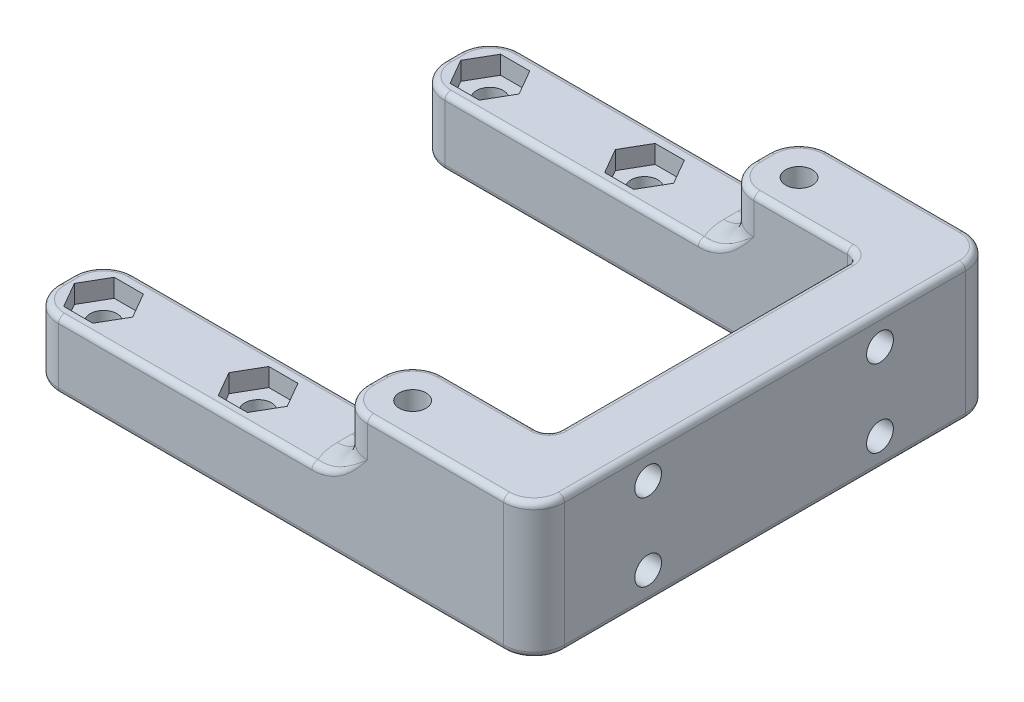
SolidWorks part; units mm, degrees
ref_plane "Front Plane" through (0, 0, 0) normal (0, 0, 1) x (1, 0, 0)
ref_plane "Top Plane" through (0, 0, 0) normal (0, 1, 0) x (1, 0, 0)
ref_plane "Right Plane" through (0, 0, 0) normal (1, 0, 0) x (0, 0, -1)
sketch "Sketch1" plane through (0, 0, 0) normal (0, 1, 0) x (1, 0, 0)
  line L0 (0, 0) -> (73.15, 0)
  line L1 (73.15, 0) -> (73.15, -51.1048)
  line L2 (73.15, -51.1048) -> (0, -51.1048)
  line L3 (0, -51.1048) -> (0, -63.5)
  line L4 (0, -63.5) -> (83.15, -63.5)
  line L5 (83.15, -63.5) -> (83.15, 12.3952)
  line L6 (83.15, 12.3952) -> (0, 12.3952)
  line L7 (0, 12.3952) -> (0, 0)
  circle A0 centre (6.35, 6.0452) radius 2.2
  circle A1 centre (57.15, 6.0452) radius 2.2
  circle A2 centre (6.35, -57.4548) radius 2.2
  circle A3 centre (57.15, -57.4548) radius 2.2
  circle A4 centre (31.75, 6.0452) radius 2.2
  circle A5 centre (31.75, -57.4548) radius 2.2
  point P19 (0, 0)
  point P20 (0, 0)
  point P23 (0, 0)
  dimension "D5" = 4.4
  dimension "D1" = 10
  dimension "D2" = 12.3952
  dimension "D3" = 6.35
  dimension "D4" = 6.35
  dimension "D6" = 50.8
  dimension "D7" = 16
  dimension "D8" = 6.35
  dimension "D9" = 63.5
  dimension "D10" = 25.4
extrude "Boss-Extrude1" add sketch "Sketch1" along normal blind 22.2504
sketch "Sketch2" plane through (0, 0, 63.5) normal (0, 0, 1) x (1, 0, 0)
  line L1 (0, 22.2504) -> (50.8, 22.2504)
  line L2 (0, 22.2504) -> (0, 11.1252)
  line L3 (0, 11.1252) -> (50.8, 11.1252)
  line L4 (50.8, 22.2504) -> (50.8, 11.1252)
  line L5 (0, 0) -> (83.15, 0)
  line L6 (83.15, 0) -> (83.15, 22.2504)
  line L7 (83.15, 22.2504) -> (0, 22.2504)
  line L8 (0, 22.2504) -> (0, 0)
  line L9 (0, 0) -> (83.15, 0)
  line L10 (83.15, 0) -> (83.15, 22.2504)
  line L11 (83.15, 22.2504) -> (0, 22.2504)
  line L12 (0, 22.2504) -> (0, 0)
  point P2 (0, 11.1252)
  point P6 (0, 0)
  point P8 (83.15, 11.1252)
  dimension "D1" = 0
  dimension "D2" = 50.8
extrude "Cut-Extrude1" cut sketch "Sketch2" against normal through all
sketch "Sketch3" plane through (0, 11.1252, 0) normal (0, 1, 0) x (1, 0, 0)
  line L0 (36.542, 6.0452) -> (34.146, 10.1952)
  line L1 (11.142, 6.0452) -> (8.746, 10.1952)
  line L2 (8.746, 10.1952) -> (3.954, 10.1952)
  line L3 (3.954, 10.1952) -> (1.558, 6.0452)
  line L4 (1.558, 6.0452) -> (3.954, 1.8952)
  line L5 (3.954, 1.8952) -> (8.746, 1.8952)
  line L6 (8.746, 1.8952) -> (11.142, 6.0452)
  line L7 (34.146, 10.1952) -> (29.354, 10.1952)
  line L8 (29.354, 10.1952) -> (26.958, 6.0452)
  line L9 (26.958, 6.0452) -> (29.354, 1.8952)
  line L10 (29.354, 1.8952) -> (34.146, 1.8952)
  line L11 (34.146, 1.8952) -> (36.542, 6.0452)
  line L12 (36.542, -57.4548) -> (34.146, -53.3048)
  line L13 (34.146, -53.3048) -> (29.354, -53.3048)
  line L14 (29.354, -53.3048) -> (26.958, -57.4548)
  line L15 (26.958, -57.4548) -> (29.354, -61.6048)
  line L16 (29.354, -61.6048) -> (34.146, -61.6048)
  line L17 (34.146, -61.6048) -> (36.542, -57.4548)
  line L18 (11.142, -57.4548) -> (8.746, -53.3048)
  line L19 (8.746, -53.3048) -> (3.954, -53.3048)
  line L20 (3.954, -53.3048) -> (1.558, -57.4548)
  line L21 (1.558, -57.4548) -> (3.954, -61.6048)
  line L22 (3.954, -61.6048) -> (8.746, -61.6048)
  line L23 (8.746, -61.6048) -> (11.142, -57.4548)
  circle A0 centre (6.35, 6.0452) radius 4.15 construction
  dimension "D3" = 8.3
  dimension "D1" = 2
  dimension "D2" = 2
extrude "Cut-Extrude2" cut sketch "Sketch3" against normal blind 3
fillet "Fillet3" radius 5 4 edges at (0, 5.5626, -12.3952) (0, 5.5626, 0) (0, 5.5626, 51.1048) (0, 5.5626, 63.5)
sketch "Sketch4" plane through (83.15, 0, 0) normal (1, 0, 0) x (0, 0, -1)
  line L0 (-51.1048, 22.2504) -> (-51.1048, 0) construction
  line L1 (-51.1048, 22.2504) -> (-51.1048, 0)
  line L2 (-51.1048, 11.1252) -> (-32.6546, 11.1252) construction
  circle A0 centre (-44.7548, 17.4752) radius 2.2
  circle A1 centre (-6.6548, 17.4752) radius 2.2
  circle A2 centre (-6.6548, 4.7752) radius 2.2
  circle A3 centre (-44.7548, 4.7752) radius 2.2
  point P6 (-51.1048, 11.1252)
  dimension "D3" = 4.4
  dimension "D1" = 6.35
  dimension "D2" = 6.35
  dimension "D4" = 2
  dimension "D5" = 2
extrude "Cut-Extrude3" cut sketch "Sketch4" against normal up to next contours A0 | A3 | A2 | A1
fillet "Fillet4" radius 5 6 edges at (83.15, 11.1252, -12.3952) (83.15, 11.1252, 63.5) (50.8, 16.6878, 51.1048) (50.8, 16.6878, 63.5) (50.8, 16.6878, -12.3952) (50.8, 16.6878, 0)
fillet "Fillet5" radius 5 6 edges at (52.2645, 11.1252, 52.5693) (52.2645, 11.1252, 62.0355) (52.2645, 11.1252, -10.9307) (52.2645, 11.1252, -1.4645) (50.8, 11.1252, 57.3024) (50.8, 11.1252, -6.1976)
fillet "Fillet6" radius 2 2 edges at (73.15, 11.1252, 51.1048) (73.15, 11.1252, 0)
fillet "Fillet7" radius 1 46 edges at (52.2645, 22.2504, 62.0355) (50.8, 22.2504, 57.3024) (52.2645, 22.2504, 52.5693) (63.475, 22.2504, 51.1048) (72.5642, 22.2504, 50.519) (73.15, 22.2504, 25.5524) (72.5642, 22.2504, 0.5858) (63.475, 22.2504, 0) (52.2645, 22.2504, -1.4645) (50.8, 22.2504, -6.1976) (52.2645, 22.2504, -10.9307) (66.975, 22.2504, -12.3952) (81.6855, 22.2504, -10.9307) (83.15, 22.2504, 25.5524) (81.6855, 22.2504, 62.0355) (41.575, 0, 63.5) (81.6855, 0, 62.0355) (83.15, 0, 25.5524) (81.6855, 0, -10.9307) (41.575, 0, -12.3952) (1.4645, 0, -10.9307) (0, 0, -6.1976) (1.4645, 0, -1.4645) (38.075, 0, 0) (72.5642, 0, 0.5858) (73.15, 0, 25.5524) (72.5642, 0, 50.519) (38.075, 0, 51.1048) (1.4645, 0, 52.5693) (0, 0, 57.3024) (49.6397, 11.572, 63.5) (26.0699, 11.1252, 63.5) (1.4645, 11.1252, 62.0355) (0, 11.1252, 57.3024) (1.4645, 11.1252, 52.5693) (49.6397, 11.572, 51.1048) (49.6397, 11.572, 0) (49.6397, 11.572, -12.3952) (26.0699, 11.1252, -12.3952) (1.4645, 11.1252, -10.9307) (0, 11.1252, -6.1976) (1.4645, 11.1252, -1.4645) (66.975, 22.2504, 63.5) (1.4645, 0, 62.0355) (26.0699, 11.1252, 51.1048) (26.0699, 11.1252, 0)
